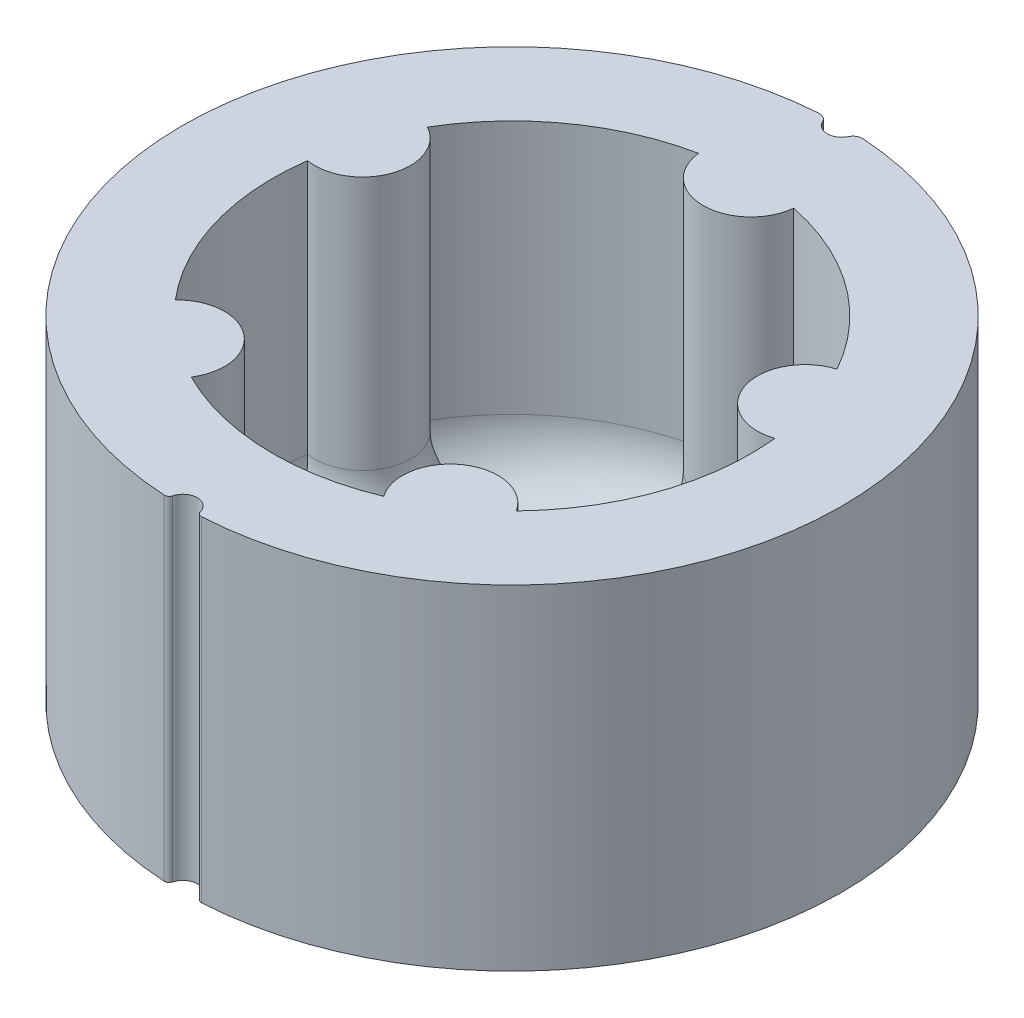
SolidWorks part; units mm, degrees
ref_plane "Front Plane" through (0, 0, 0) normal (0, 0, 1) x (1, 0, 0)
ref_plane "Top Plane" through (0, 0, 0) normal (0, 1, 0) x (1, 0, 0)
ref_plane "Right Plane" through (0, 0, 0) normal (1, 0, 0) x (0, 0, -1)
sketch "Sketch1" plane through (0, 0, 0) normal (0, 1, 0) x (1, 0, 0)
  line L3 (0, 0.002) -> (0, 3.7877) construction
  line L4 (0, 3.7877) -> (2.417, 3.7877)
  line L5 (0, 3.7877) -> (-2.417, 3.7877)
  arc A0 (1.9642, -34.442) -> (34.1982, 4.5552) centre (0, 0.002) ccw
  arc A2 (-2.417, 3.7877) -> (2.417, 3.7877) centre (0, 0.002) ccw
  circle A3 centre (0, 0.002) radius 34.5 construction
  arc A7 (-1.3541, 33.8562) -> (1.3541, 33.8562) centre (0, 34.5015) ccw
  arc A8 (34.1982, 4.5552) -> (2.3241, 34.4236) centre (0, 0.002) ccw
  arc A9 (-2.3241, 34.4236) -> (-34.1982, 4.5552) centre (0, 0.002) ccw
  arc A10 (-34.1982, 4.5552) -> (-1.9642, -34.442) centre (0, 0.002) ccw
  arc A11 (1.3541, 33.8562) -> (2.3241, 34.4236) centre (2.2568, 33.4259) cw
  arc A12 (-1.3541, 33.8562) -> (-2.3241, 34.4236) centre (-2.2568, 33.4259) ccw
  arc A13 (1.4518, -34.0686) -> (-1.4518, -34.0686) centre (0, -34.4457) ccw
  arc A14 (1.4518, -34.0686) -> (1.9642, -34.442) centre (1.9358, -33.9428) ccw
  arc A15 (-1.4518, -34.0686) -> (-1.9642, -34.442) centre (-1.9358, -33.9428) cw
  point P15 (1.4997, 34.4694)
  dimension "D2" = 4.834
  dimension "D3" = 4.4915
  dimension "D4" = 34.5
  dimension "D5" = 1
  dimension "D6" = 1.5
  dimension "D7" = 0.5
  dimension "D11" = 1.4997
sketch "Sketch2" plane through (0, 0, 0) normal (0, 1, 0) x (1, 0, 0)
  arc A39 (-24.7719, 3.3696) -> (-19.066, -16.1705) centre (0, 0) ccw
  circle A40 centre (0, 0) radius 20 construction
  arc A41 (-4.9749, 24.5) -> (4.9749, 24.5) centre (0, 25) ccw
  arc A42 (21.8332, 12.1783) -> (24.8593, 2.6482) centre (23.2806, 7.3924) ccw
  arc A43 (17.9078, -17.4445) -> (9.6395, -23.0668) centre (13.7289, -20.1898) ccw
  arc A44 (-11.2459, -22.3278) -> (-19.066, -16.1705) centre (-15.455, -19.6289) ccw
  arc A45 (-24.7719, 3.3696) -> (-21.5415, 12.6871) centre (-23.9399, 8.2999) ccw
  arc A46 (-4.9749, 24.5) -> (-21.5415, 12.6871) centre (0, 0) ccw
  arc A47 (21.8332, 12.1783) -> (4.9749, 24.5) centre (0, 0) ccw
  arc A48 (17.9078, -17.4445) -> (24.8593, 2.6482) centre (0, 0) ccw
  arc A49 (-11.2459, -22.3278) -> (9.6395, -23.0668) centre (0, 0) ccw
  dimension "D1" = 50
  dimension "D2" = 40
extrude "Boss-Extrude1" add sketch "Sketch1" along normal blind 35 contours A10 A0 A8 A7 A9 A2 L5 L4 region at (2.2155, 0, 33.5591)
extrude "Cut-Extrude2" cut sketch "Sketch2" along normal through all
extrude "Boss-Extrude2" add sketch "Sketch2<2>" along normal blind 0.4
sketch "Sketch2<2>" plane through (0, 0, 0) normal (0, 1, 0) x (1, 0, 0) same geometry as "Sketch2"
fillet "Fillet1" radius 8 10 edges at (18.5151, 0.4, -5.8792) (23.626, 0.4, 8.174) (10.9173, 0.4, 16.0551) (-0.8841, 0.4, 24.9844) (-12.3619, 0.4, 15.7005) (-23.9978, 0.4, 7.0075) (-19.2158, 0.4, -6.6621) (-14.5144, 0.4, -20.3552) (0, 0.4, -20) (14.7521, 0.4, -20.1835)
equation "\"2.5.00mm\"=3"
